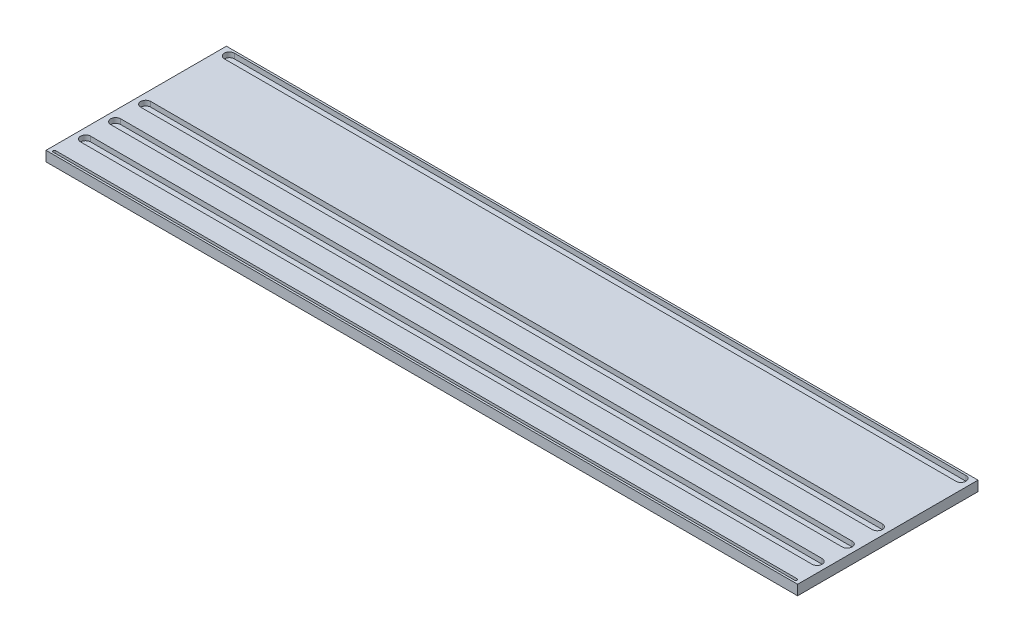
SolidWorks part; units mm, degrees
ref_plane "Front Plane" through (0, 0, 0) normal (0, 0, 1) x (1, 0, 0)
ref_plane "Top Plane" through (0, 0, 0) normal (0, 1, 0) x (1, 0, 0)
ref_plane "Right Plane" through (0, 0, 0) normal (1, 0, 0) x (0, 0, -1)
sketch "Sketch1" plane through (0, 0, 0) normal (0, 1, 0) x (1, 0, 0)
  line L1 (0, 0) -> (476.25, 0)
  line L2 (0, 0) -> (0, 114.3)
  line L3 (0, 114.3) -> (476.25, 114.3)
  line L4 (476.25, 0) -> (476.25, 114.3)
  dimension "D1" = 114.3
  dimension "D2" = 476.25
extrude "Boss-Extrude1" add sketch "Sketch1" against normal blind 6.35
sketch "Sketch2" plane through (0, 0, 0) normal (0, 1, 0) x (1, 0, 0)
  line L1 (6.35, 21.9075) -> (469.9, 21.9075)
  line L2 (6.35, 21.9075) -> (6.35, 15.5575)
  line L3 (6.35, 15.5575) -> (469.9, 15.5575)
  line L4 (469.9, 21.9075) -> (469.9, 15.5575)
  line L5 (6.35, 40.9575) -> (469.9, 40.9575)
  line L6 (6.35, 40.9575) -> (6.35, 34.6075)
  line L7 (6.35, 34.6075) -> (469.9, 34.6075)
  line L8 (469.9, 40.9575) -> (469.9, 34.6075)
  line L9 (6.35, 60.0075) -> (469.9, 60.0075)
  line L10 (6.35, 60.0075) -> (6.35, 53.6575)
  line L11 (6.35, 53.6575) -> (469.9, 53.6575)
  line L12 (469.9, 60.0075) -> (469.9, 53.6575)
  line L13 (3.175, 2.8575) -> (473.075, 2.8575)
  line L14 (3.175, 2.8575) -> (3.175, 1.27)
  line L15 (3.175, 1.27) -> (473.075, 1.27)
  line L16 (473.075, 2.8575) -> (473.075, 1.27)
  line L17 (6.35, 106.68) -> (469.9, 106.68)
  line L18 (6.35, 106.68) -> (6.35, 113.03)
  line L19 (6.35, 113.03) -> (469.9, 113.03)
  line L20 (469.9, 106.68) -> (469.9, 113.03)
  arc A0 (6.35, 53.6575) -> (6.35, 60.0075) centre (6.35, 56.8325) cw
  arc A1 (6.35, 34.6075) -> (6.35, 40.9575) centre (6.35, 37.7825) cw
  arc A2 (6.35, 15.5575) -> (6.35, 21.9075) centre (6.35, 18.7325) cw
  arc A3 (3.175, 1.27) -> (3.175, 2.8575) centre (3.175, 2.0638) cw
  arc A4 (469.9, 60.0075) -> (469.9, 53.6575) centre (469.9, 56.8325) cw
  arc A5 (469.9, 40.9575) -> (469.9, 34.6075) centre (469.9, 37.7825) cw
  arc A6 (469.9, 21.9075) -> (469.9, 15.5575) centre (469.9, 18.7325) cw
  arc A7 (473.075, 2.8575) -> (473.075, 1.27) centre (473.075, 2.0638) cw
  arc A8 (6.35, 106.68) -> (6.35, 113.03) centre (6.35, 109.855) cw
  arc A10 (469.9, 106.68) -> (469.9, 113.03) centre (469.9, 109.855) ccw
  dimension "D1" = 463.55
  dimension "D2" = 6.35
  dimension "D3" = 6.35
  dimension "D4" = 6.35
  dimension "D5" = 1.5875
  dimension "D6" = 463.55
  dimension "D7" = 463.55
  dimension "D8" = 3.175
  dimension "D9" = 3.175
  dimension "D10" = 6.35
  dimension "D11" = 12.7
  dimension "D13" = 6.35
  dimension "D14" = 1.27
  dimension "D15" = 1.27
  dimension "D17" = 12.7
  dimension "D18" = 12.7
  dimension "D19" = 463.55
extrude "Cut-Extrude1" cut sketch "Sketch2" against normal blind 3.175 contours L17 L20 L19 L18 | A8 L18 | L12 L9 L10 L11 | A0 L10 | L8 L5 L6 L7 | A1 L6 | A2 L2 | A3 L14 | L20 A10 | A4 L12 | A5 L8 | A6 L4 | A7 L16 region at (5.0025, 0, -18.7325) region at (471.2475, 0, -18.7325) region at (238.125, 0, -37.7825) region at (5.0025, 0, -37.7825) region at (471.2475, 0, -37.7825) region at (238.125, 0, -56.8325) region at (5.0025, 0, -56.8325) region at (471.2475, 0, -56.8325) region at (2.8381, 0, -2.0638) region at (473.4119, 0, -2.0637) region at (238.125, 0, -109.855) region at (5.0025, 0, -109.855) region at (471.2475, 0, -109.855)
extrude "Cut-Extrude2" cut sketch "Sketch2<3>" against normal blind 3.175 contours L4 L1 L2 L3 | L16 L13 L14 L15 region at (238.125, 0, -18.7325) region at (238.125, 0, -2.0638)
sketch "Sketch2<3>" plane through (0, 0, 0) normal (0, 1, 0) x (1, 0, 0) same geometry as "Sketch2"
